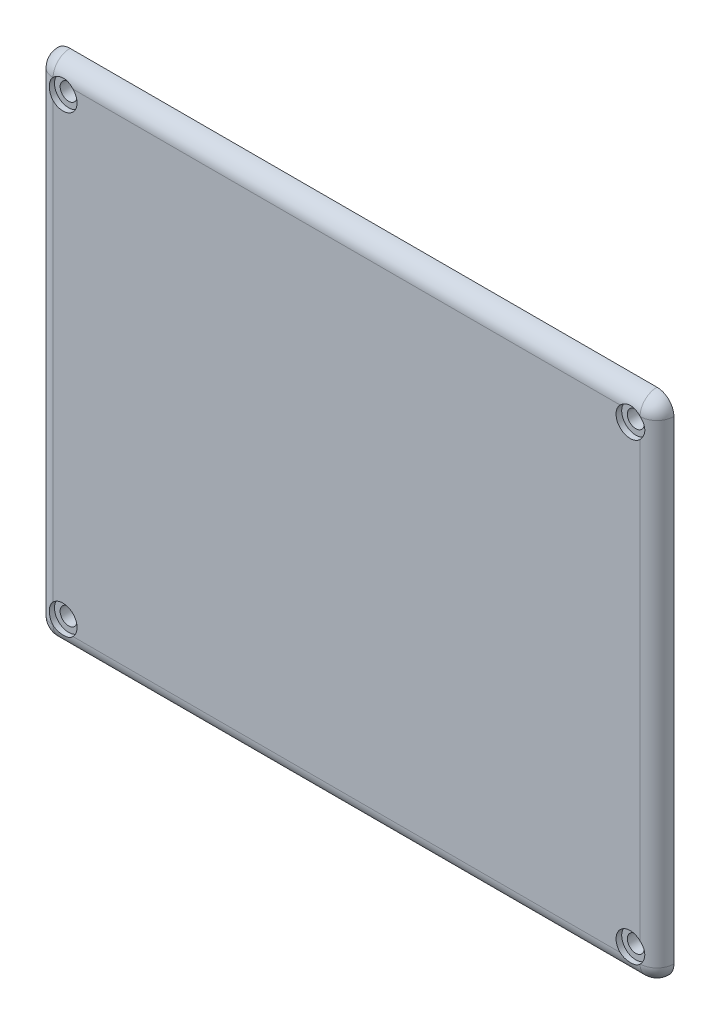
SolidWorks part; units mm, degrees
ref_plane "Płaszczyzna przednia" through (0, 0, 0) normal (0, 0, 1) x (1, 0, 0)
ref_plane "Płaszczyzna górna" through (0, 0, 0) normal (0, 1, 0) x (1, 0, 0)
ref_plane "Płaszczyzna prawa" through (0, 0, 0) normal (1, 0, 0) x (0, 0, -1)
sketch "Sketch1" plane through (0, 0, 0) normal (0, 0, 1) x (1, 0, 0)
  line L1 (52, -45) -> (-52, -45)
  line L2 (55, -42) -> (55, 42)
  line L3 (52, 45) -> (-52, 45)
  line L4 (-55, -42) -> (-55, 42)
  line L5 (55, -45) -> (-55, 45) construction
  line L6 (55, 45) -> (-55, -45) construction
  arc A0 (52, -45) -> (55, -42) centre (52, -42) ccw
  arc A1 (-52, -45) -> (-55, -42) centre (-52, -42) cw
  arc A2 (55, 42) -> (52, 45) centre (52, 42) ccw
  arc A3 (-52, 45) -> (-55, 42) centre (-52, 42) ccw
  point P0 (0, 0)
  dimension "D3" = 3
  dimension "D1" = 110
  dimension "D2" = 90
extrude "Boss-Extrude1" add sketch "Sketch1" along normal blind 3
fillet "Fillet3" radius 3 8 edges at (0, -45, 3) (-54.1213, -44.1213, 3) (-55, 0, 3) (-54.1213, 44.1213, 3) (0, 45, 3) (54.1213, 44.1213, 3) (55, 0, 3) (54.1213, -44.1213, 3)
sketch "Sketch2" plane through (0, 0, 3) normal (0, 0, 1) x (1, 0, 0)
  line L0 (52, 45) -> (-52, 45) construction
  line L1 (-55, 42) -> (-55, -42) construction
  line L2 (55, -42) -> (55, 42) construction
  line L3 (-52, -45) -> (52, -45) construction
  circle A0 centre (-50.25, 40.25) radius 4.75 construction
  circle A1 centre (-50.25, 40.25) radius 1.5
  circle A2 centre (50.25, 40.25) radius 4.75 construction
  circle A3 centre (50.25, 40.25) radius 1.5
  circle A4 centre (-50.25, -40.25) radius 4.75 construction
  circle A5 centre (-50.25, -40.25) radius 1.5
  circle A6 centre (50.25, -40.25) radius 4.75 construction
  circle A7 centre (50.25, -40.25) radius 1.5
  point P24 (0, 0)
  dimension "D1" = 9.5
  dimension "D2" = 3
  dimension "D3" = 9.5
  dimension "D4" = 3
  dimension "D5" = 9.5
  dimension "D6" = 3
  dimension "D7" = 9.5
  dimension "D8" = 3
extrude "Cut-Extrude1" cut sketch "Sketch2" against normal through all
sketch "Sketch3" plane through (0, 0, 3) normal (0, 0, 1) x (1, 0, 0)
  circle A0 centre (-50.25, 40.25) radius 2.5
  circle A1 centre (-50.25, 40.25) radius 1.5 construction
  circle A2 centre (50.25, 40.25) radius 2.5
  circle A3 centre (50.25, 40.25) radius 1.5 construction
  circle A4 centre (-50.25, -40.25) radius 2.5
  circle A5 centre (-50.25, -40.25) radius 1.5 construction
  circle A6 centre (50.25, -40.25) radius 2.5
  circle A7 centre (50.25, -40.25) radius 1.5 construction
  dimension "D1" = 5
  dimension "D2" = 5
  dimension "D3" = 5
  dimension "D4" = 5
extrude "Cut-Extrude2" cut sketch "Sketch3" against normal blind 1
